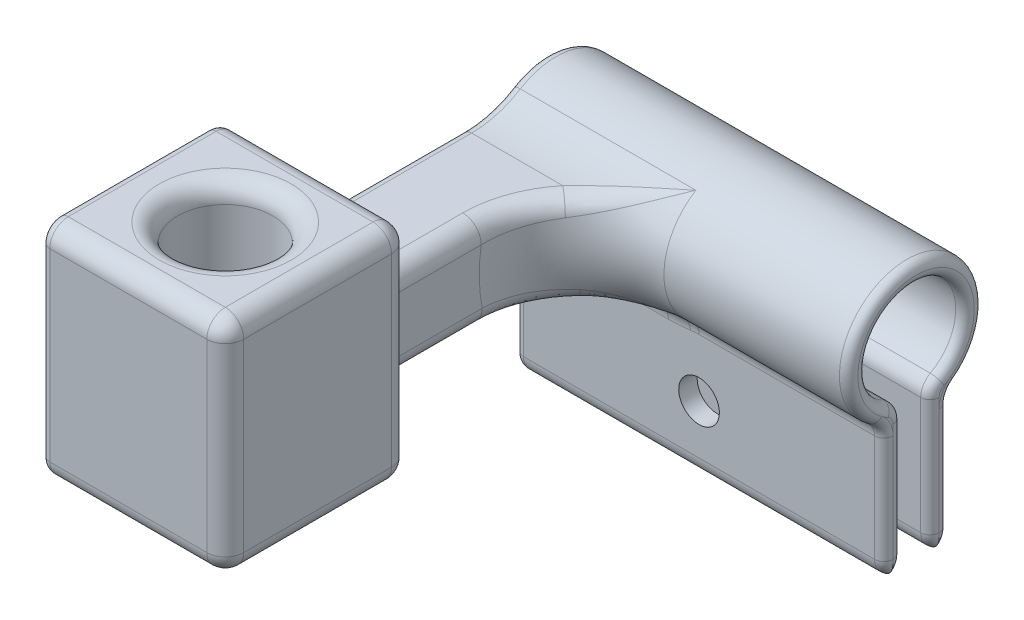
SolidWorks part; units mm, degrees
ref_plane "Front Plane" through (0, 0, 0) normal (0, 0, 1) x (1, 0, 0)
ref_plane "Top Plane" through (0, 0, 0) normal (0, 1, 0) x (1, 0, 0)
ref_plane "Right Plane" through (0, 0, 0) normal (1, 0, 0) x (0, 0, -1)
sketch "Sketch1" plane through (0, 0, 0) normal (0, 1, 0) x (1, 0, 0)
  line L0 (-5, 0) -> (5, 0) construction
  line L1 (-5, 5) -> (5, 5)
  line L2 (-5, 5) -> (-5, -5)
  line L3 (-5, -5) -> (5, -5)
  line L4 (5, 5) -> (5, -5)
  circle A0 centre (0, 0) radius 2.575
  point P9 (0, 0)
  dimension "D1" = 5.15
  dimension "D2" = 10
extrude "Boss-Extrude1" add sketch "Sketch1" along normal blind 10
extrude "Boss-Extrude2" add sketch "Sketch1<2>" against normal blind 2 contours L0 A0 | A0 L0 | L2 L0 A0 L4 L1 | L0 L2 L3 L4 A0 region at (0, 0, -2.8702) region at (0, 0, 1.0929) region at (0, 0, -1.0929) region at (0, 0, 2.8702)
sketch "Sketch1<2>" plane through (0, 0, 0) normal (0, 1, 0) x (1, 0, 0) same geometry as "Sketch1"
sketch "Sketch3" plane through (-5, 0, 0) normal (-1, 0, 0) x (0, 0, 1)
  line L0 (5, 0.65) -> (-5, 0.65) construction
  line L1 (5, 10) -> (5, -2) construction
  line L2 (-5, 10) -> (-5, -2) construction
  line L3 (-5, 0.65) -> (-22.4, 0.65) construction
  line L4 (-22.4, 0.65) -> (-22.4, -2) construction
  line L5 (-21.65, -1.8917) -> (-20.65, -1.8917)
  line L6 (-21.65, -1.8917) -> (-21.65, -9.8917)
  line L7 (-21.65, -9.8917) -> (-20.65, -9.8917)
  line L8 (-20.65, -1.8917) -> (-20.65, -9.8917)
  line L9 (-23.15, -9.8917) -> (-24.15, -9.8917)
  line L10 (-24.15, -1.8917) -> (-24.15, -9.8917)
  line L11 (-23.15, -1.8917) -> (-24.15, -1.8917)
  line L12 (-23.15, -1.8917) -> (-23.15, -9.8917)
  line L15 (-5, -2) -> (5, -2) construction
  circle A1 centre (-22.4, 0.65) radius 2.65
  circle A2 centre (-22.4, 0.65) radius 3.65
  point P9 (0, 0.65)
  point P19 (-22.4, -0.1163)
  point P21 (0, 0)
  point P22 (0, 0)
  dimension "D1" = 5.3
  dimension "D2" = 1
  dimension "D3" = 22.4
  dimension "D4" = 1
  dimension "D5" = 1.5
  dimension "D6" = 8
extrude "Boss-Extrude3" add sketch "Sketch3" against normal blind 20 separate body contours L8 A2 L10 L11 A1 L5 | L10 A2 L12 L11 | L6 A2 L8 L5 | A2 L6 L7 L8 | A2 L10 L9 L12 region at (-5, -0.9966, -20.1973) region at (-5, -2.3351, -21.185) region at (-5, -6.3278, -21.1457) region at (-5, -2.3351, -23.615) region at (-5, -6.3278, -23.6543)
sketch "Sketch4" plane through (0, 0, -24.15) normal (0, 0, -1) x (-1, 0, 0)
  line L0 (-15, -2.5531) -> (5, -2.5531) construction
  line L1 (-15, -2.5531) -> (5, -2.5531) construction
  line L2 (-5, -2.5531) -> (-5, -9.8917) construction
  line L3 (-15, -9.8917) -> (5, -9.8917) construction
  circle A0 centre (-5, -6.2224) radius 1.1
  dimension "D1" = 2.2
extrude "Cut-Extrude1" cut sketch "Sketch4" against normal up to surface (3.5 mm away) up to face at (5, -6.2224, -20.65)
sketch "Sketch5" plane through (0, 0, -5) normal (0, 0, -1) x (-1, 0, 0)
  line L0 (5, -2) -> (-5, -2) construction
  line L1 (5, 10) -> (5, -2) construction
  line L2 (5, -2) -> (-5, -2) construction
  line L3 (5, 10) -> (5, -2) construction
  line L5 (5, -2) -> (0, -2)
  line L6 (5, -2) -> (5, 3)
  line L7 (5, 3) -> (0, 3)
  line L8 (0, -2) -> (0, 3)
  dimension "D1" = 5
extrude "Boss-Extrude4" add sketch "Sketch5" along normal up to next
sketch "Sketch6" plane through (-5, 0, 0) normal (-1, 0, 0) x (0, 0, 1)
  line L0 (0, 10) -> (0, -2) construction
  line L1 (-5, 10) -> (5, 10) construction
  line L2 (-19.89, -2) -> (5, -2) construction
  circle A0 centre (0, 4) radius 1.35
  point P9 (0, 0)
  point P10 (0, 4)
  dimension "D1" = 2.7
extrude "Cut-Extrude2" cut sketch "Sketch6" against normal up to next contours A0
fillet "Fillet1" radius 5 3 edges at (0, 0.4438, -18.7558) (-2.5, 3, -19.6072) (-2.5, -2, -19.89)
fillet "Fillet2" radius 1 26 edges at (5, -1.8917, -21.65) (5, -1.8917, -23.15) (5, -9.8917, -24.15) (5, -9.8917, -23.15) (5, -9.8917, -21.65) (5, -9.8917, -20.65) (5, -2.5531, -24.15) (10, -2.5531, -20.65) (4.6857, -2.4831, -20.5083) (0.5641, -2, -16.6372) (0, -2, -9.583) (3.2241, 3.246, -19.3885) (0.4418, 3, -16.2378) (0, 3, -9.5377) (2.5, -2, -5) (5, -2, 0) (5, 10, 0) (5, 4, 5) (5, 4, -5) (0, 0.5, -5) (-2.5, 3, -5) (0, -2, 5) (0, 10, 5) (0, 10, -5) (0, 10, 2.575) (0, -2.5531, -20.65)
fillet "Fillet3" radius 0.5 40 edges at (-5, -2, -7.1821) (-5, -9.3917, -20.784) (-5, -9.3917, -24.016) (-5, -5.9957, -24.15) (-5, -2.6477, -24.258) (-5, 2.6931, -25.4246) (-5, 3.1915, -19.2099) (-5, -9.3917, -21.516) (-5, -5.7224, -21.65) (-5, -2.043, -21.5101) (-5, -9.3917, -23.284) (-5, -5.7224, -23.15) (-5, -2.043, -23.2899) (-5, -2.0668, -19.1787) (-5, -6.052, -20.65) (-5, 4, 5) (-5, 10, 0) (-5, 3, -11.9196) (-5, 6.5, -5) (-5, 4, 1.35) (-5, 3.3, -22.4) (-5, -1.7071, 4.7071) (-5, 9.7071, 4.7071) (-5, 9.7071, -4.7071) (-5, 3.2929, -5.2929) (15, -9.3917, -21.516) (15, -9.3917, -20.784) (15, -5.9957, -20.65) (15, -2.6477, -20.542) (15, 4.3, -22.4) (15, -2.6477, -24.258) (15, -5.9957, -24.15) (15, -9.3917, -24.016) (15, -9.3917, -23.284) (15, -5.7224, -23.15) (15, -2.043, -23.2899) (15, 3.3, -22.4) (15, -2.043, -21.5101) (15, -5.7224, -21.65) (-5, -2.6299, -20.4629)
